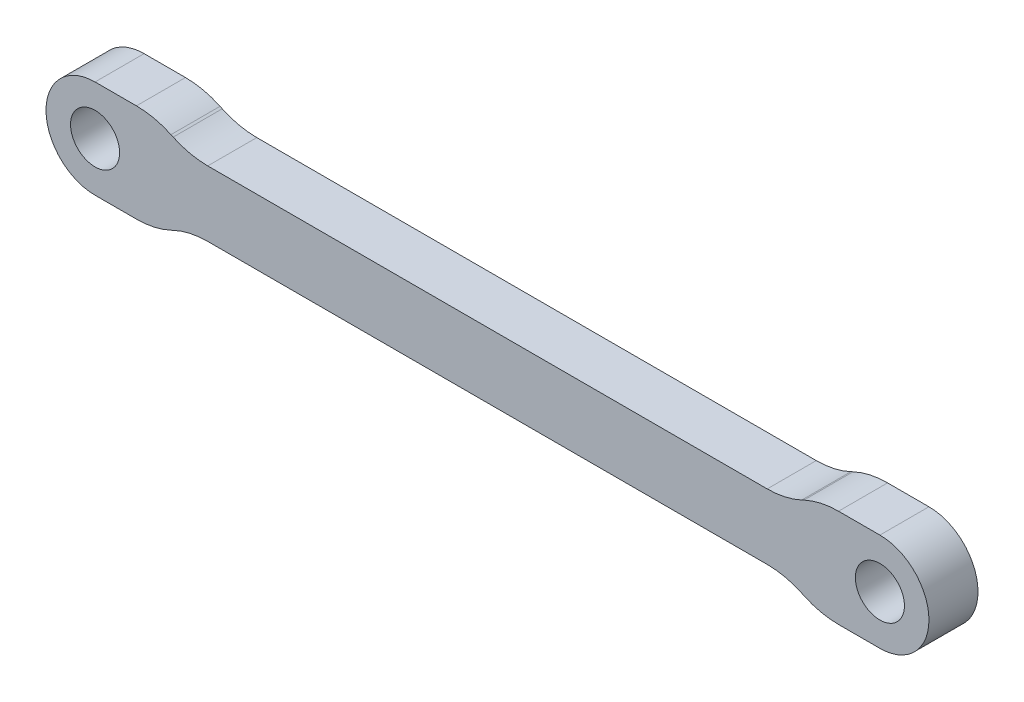
SolidWorks part; units mm, degrees
material "ABS"
ref_plane "Front Plane" through (0, 0, 0) normal (0, 0, 1) x (1, 0, 0)
ref_plane "Top Plane" through (0, 0, 0) normal (0, 1, 0) x (1, 0, 0)
ref_plane "Right Plane" through (0, 0, 0) normal (1, 0, 0) x (0, 0, -1)
sketch "Sketch1" plane through (0, 0, 0) normal (0, 0, 1) x (1, 0, 0)
  line L0 (0, 0) -> (96, 0) construction
  line L1 (0, 6) -> (96, 6)
  line L2 (0, -6) -> (96, -6)
  circle A0 centre (0, 0) radius 3
  circle A1 centre (96, 0) radius 3
  arc A2 (0, 6) -> (0, -6) centre (0, 0) ccw
  arc A3 (96, -6) -> (96, 6) centre (96, 0) ccw
  point P5 (48, 0)
  dimension "D1" = 6
  dimension "D2" = 6
  dimension "D3" = 96
  dimension "D4" = 6
extrude "Boss-Extrude2" add sketch "Sketch1" along normal blind 6
sketch "Sketch2" plane through (0, 0, 6) normal (0, 0, 1) x (1, 0, 0)
  line L0 (0, 0) -> (96, 0) construction
  line L1 (48, 28.1254) -> (48, -35.1878) construction
  line L2 (0, -6) -> (96, -6) construction
  line L3 (18, -8) -> (78, -8)
  line L4 (18, -8) -> (18, -4)
  line L5 (18, -4) -> (78, -4)
  line L6 (78, -8) -> (78, -4)
  line L7 (18, -8) -> (78, -4) construction
  line L8 (18, -4) -> (78, -8) construction
  line L9 (96, 6) -> (0, 6) construction
  line L10 (78, 4) -> (18, 4)
  line L11 (78, 4) -> (78, 8)
  line L12 (78, 8) -> (18, 8)
  line L13 (18, 4) -> (18, 8)
  line L14 (78, 4) -> (18, 8) construction
  line L15 (78, 8) -> (18, 4) construction
  point P6 (48, -6)
  point P13 (48, 6)
  dimension "D1" = 4
  dimension "D2" = 4
  dimension "D3" = 30
extrude "Cut-Extrude2" cut sketch "Sketch2" against normal through all
chamfer "Chamfer2" distance 5 angle 65 4 edges at (78, 6, 3) (78, -6, 3) (18, -6, 3) (18, 6, 3) first distance on face at (78, 5, 3) first distance on face at (78, -5, 3) first distance on face at (18, -5, 3) first distance on face at (18, 5, 3)
fillet "Fillet2" radius 10 8 edges at (11.5665, -4, 3) (7.2775, -6, 3) (84.4335, -4, 3) (88.7225, -6, 3) (84.4335, 4, 3) (88.7225, 6, 3) (11.5665, 4, 3) (7.2775, 6, 3)
